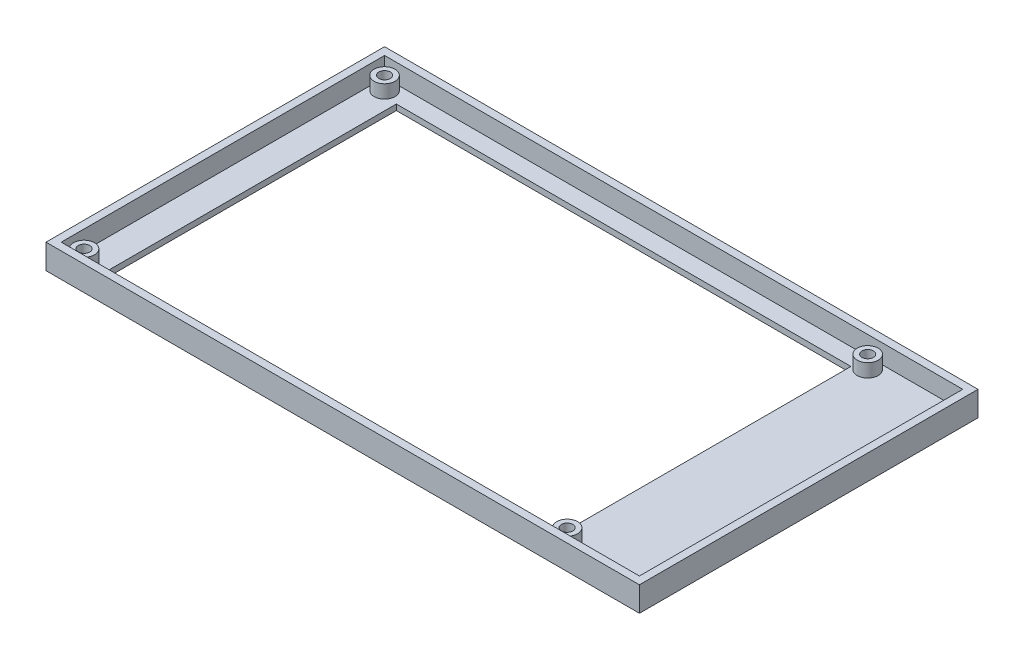
SolidWorks part; units mm, degrees
ref_plane "Alzado" through (0, 0, 0) normal (0, 0, 1) x (1, 0, 0)
ref_plane "Planta" through (0, 0, 0) normal (0, 1, 0) x (1, 0, 0)
ref_plane "Vista lateral" through (0, 0, 0) normal (1, 0, 0) x (0, 0, -1)
sketch "Croquis1" plane through (0, 0, 0) normal (0, 1, 0) x (1, 0, 0)
  line L1 (0, 0) -> (152, 0)
  line L2 (0, 0) -> (0, 85)
  line L3 (0, 85) -> (152, 85)
  line L4 (152, 0) -> (152, 85)
  dimension "D1" = 152
  dimension "D2" = 85
extrude "Saliente-Extruir1" add sketch "Croquis1" along normal blind 1.5
sketch "Croquis2" plane through (0, 1.5, 0) normal (0, 1, 0) x (1, 0, 0)
  line L0 (154, 87) -> (-2, 87)
  line L1 (-2, 87) -> (-2, -2)
  line L2 (-2, -2) -> (154, -2)
  line L3 (154, -2) -> (154, 87)
  line L4 (0, 85) -> (0, 0)
  line L5 (0, 0) -> (152, 0)
  line L6 (152, 0) -> (152, 85)
  line L7 (152, 85) -> (0, 85)
  line L8 (0, 85) -> (0, 0)
  line L9 (0, 0) -> (152, 0)
  line L10 (152, 0) -> (152, 85)
  line L11 (152, 85) -> (0, 85)
  dimension "D1" = 0
  dimension "D2" = 2
extrude "Saliente-Extruir3" add sketch "Croquis2" against normal up to surface (1.5 mm away) and the other way blind 5 up to face at (76, 0, -42.5)
sketch "Croquis3" plane through (0, 1.5, 0) normal (0, 1, 0) x (1, 0, 0)
  line L0 (0, 85) -> (0, 0) construction
  line L1 (152, 85) -> (0, 85) construction
  line L2 (76, 85) -> (76, 0) construction
  line L3 (0, 0) -> (152, 0) construction
  line L4 (0, 42.5) -> (152, 42.5) construction
  line L5 (0, 85) -> (0, 0) construction
  line L6 (152, 0) -> (152, 85) construction
  circle A0 centre (3, 82) radius 2.75
  circle A3 centre (3, 3) radius 2.75
  circle A4 centre (130, 82) radius 2.75
  circle A5 centre (130, 3) radius 2.75
  dimension "D1" = 5.5
  dimension "D4" = 5.5
  dimension "D2" = 3
  dimension "D3" = 3
  dimension "D5" = 127
  dimension "D6" = 3
extrude "Saliente-Extruir4" add sketch "Croquis3" along normal blind 3.5
sketch "Croquis4" plane through (0, 0, 0) normal (0, -1, 0) x (1, 0, 0)
  line L0 (-2, -87) -> (-2, 2) construction
  line L1 (7.6, -80.5) -> (127.1, -80.5)
  line L2 (7.6, -80.5) -> (7.6, -2)
  line L3 (7.6, -2) -> (127.1, -2)
  line L4 (127.1, -80.5) -> (127.1, -2)
  line L5 (154, -87) -> (-2, -87) construction
  dimension "D1" = 119.5
  dimension "D2" = 78.5
  dimension "D3" = 9.6
  dimension "D4" = 6.5
extrude "Cortar-Extruir1" cut sketch "Croquis4" against normal up to surface (1.5 mm away) up to face at (3, 1.5, -5.75)
sketch "Croquis5" plane through (0, 5, 0) normal (0, 1, 0) x (1, 0, 0)
  circle A0 centre (130, 3) radius 1.5
  circle A1 centre (3, 3) radius 1.5
  circle A2 centre (3, 82) radius 1.5
  circle A3 centre (130, 82) radius 1.5
  point P12 (130, 82)
  point P13 (130, 82)
  dimension "D1" = 3
extrude "Cortar-Extruir2" cut sketch "Croquis5" against normal blind 3
